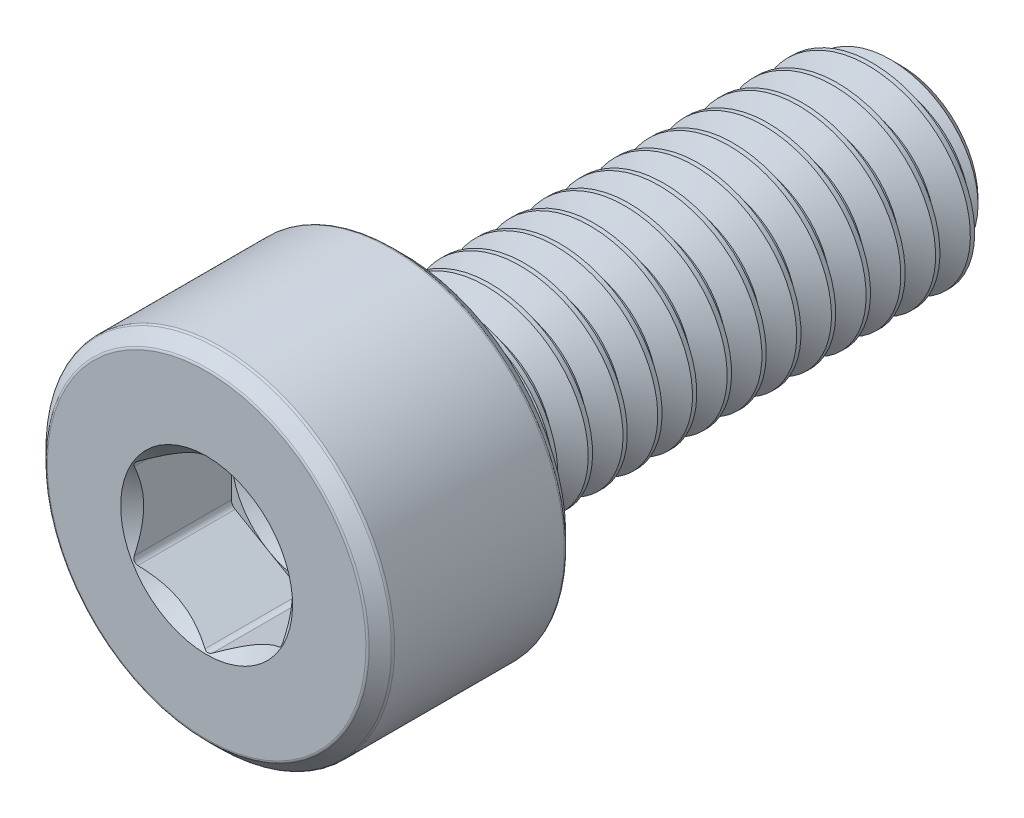
SolidWorks part; units mm, degrees
ref_plane "Front Plane" through (0, 0, 0) normal (0, 0, 1) x (1, 0, 0)
ref_plane "Top Plane" through (0, 0, 0) normal (0, 1, 0) x (1, 0, 0)
ref_plane "Right Plane" through (0, 0, 0) normal (1, 0, 0) x (0, 0, -1)
sketch "Sketch1" plane through (0, 0, 0) normal (1, 0, 0) x (0, 0, -1)
  line L0 (-7, 0) -> (7, 0) construction
  line L1 (-7, 0) -> (-7, 3.5)
  line L2 (-7, 3.5) -> (-3, 3.5)
  line L3 (-3, 3.5) -> (-3, 2)
  line L4 (-3, 2) -> (6.5453, 2)
  line L5 (6.9562, 2.0758) -> (7.3062, 1.4696) construction
  line L6 (7.3062, 1.4696) -> (7.6562, 2.0758) construction
  line L7 (7.6562, 2.0758) -> (6.9562, 2.0758) construction
  line L8 (6.5453, 2) -> (7, 1.5453)
  line L9 (7, 1.5453) -> (7, 0)
  line L10 (7, 2) -> (7.6125, 2) construction
  line L11 (7.3062, 2.0758) -> (7.3062, 2) construction
  line L12 (7.3062, 2) -> (7.3062, 1.5453) construction
  line L13 (7.3062, 1.5453) -> (7.3062, 1.4696) construction
  line L14 (7.2625, 1.5453) -> (7.35, 1.5453)
  line L15 (6.9781, 2.0379) -> (7.6344, 2.0379)
  line L16 (7.35, 1.5453) -> (7.6344, 2.0379)
  line L17 (7.2625, 1.5453) -> (6.9781, 2.0379)
  line L18 (-7, 1.5) -> (-5, 1.5)
  line L19 (-5, 1.5) -> (-5, 0)
  line L20 (4.55, 2) -> (4.55, -2) construction
  point P20 (7.3062, 2.0379)
  point P22 (4.55, -2)
  point P28 (4.55, 0)
  point P29 (6.5453, -2)
  dimension "Head Diameter" = 7
  dimension "Length" = 10
  dimension "Head Height" = 4
  dimension "Thread Size" = 4
  dimension "D1" = 45
  dimension "Thread Pitch" = 0.7
  dimension "D3" = 0.0875
  dimension "Drive Size" = 3
  dimension "D4" = 2.45
  dimension "D5" = 2
sketch "Sketch3" plane through (0, 0, 0) normal (1, 0, 0) x (0, 0, -1)
  line L0 (-7, 3.2103) -> (-7, 1.5)
  line L1 (-7, 1.5) -> (-5, 1.5)
  line L2 (-5, 1.5) -> (-5, 0)
  line L3 (-5, 0) -> (7, 0)
  line L4 (7, 0) -> (7, 1.5453)
  line L5 (7, 1.5453) -> (6.5453, 2)
  line L6 (6.5453, 2) -> (-3, 2)
  line L7 (-3, 2) -> (-3, 3.2103)
  line L8 (-3.2897, 3.5) -> (-6.7103, 3.5)
  line L9 (-6.9808, 3.2567) -> (-6.7567, 3.4808)
  line L11 (-7, 3.5) -> (-3, 3.5) construction
  line L12 (-3.2433, 3.4808) -> (-3.0192, 3.2567)
  arc A5 (-3.0192, 3.2567) -> (-3, 3.2103) centre (-3.0656, 3.2103) cw
  arc A6 (-3.2897, 3.5) -> (-3.2433, 3.4808) centre (-3.2897, 3.4344) cw
  arc A7 (-6.7103, 3.5) -> (-6.7567, 3.4808) centre (-6.7103, 3.4344) ccw
  arc A8 (-7, 3.2103) -> (-6.9808, 3.2567) centre (-6.9344, 3.2103) cw
  point P17 (-5, 3.5)
  point P29 (-7, 3.2375)
  dimension "D3" = 0.0656
  dimension "D1" = 45
  dimension "D2" = 0.2625
revolve "Revolve1" add sketch "Sketch3" angle 360 about L0
sketch "Sketch4" plane through (0, 0, 7) normal (0, 0, 1) x (1, 0, 0)
  line L1 (0, 1.7321) -> (-1.5, 0.866)
  line L2 (-1.5, 0.866) -> (-1.5, -0.866)
  line L3 (-1.5, -0.866) -> (0, -1.7321)
  line L4 (0, -1.7321) -> (1.5, -0.866)
  line L5 (1.5, -0.866) -> (1.5, 0.866)
  line L6 (1.5, 0.866) -> (0, 1.7321)
  circle A0 centre (0, 0) radius 1.5 construction
extrude "Cut-Extrude1" cut sketch "Sketch4" against normal up to vertex (2 mm away) up to point (0, 1.5, 5)
sketch "Sketch5" plane through (0, 0, 7) normal (0, 0, 1) x (1, 0, 0)
  circle A0 centre (0, 0) radius 1.7321
extrude "Cut-Extrude2" cut sketch "Sketch5" against normal up to next (2 mm away) draft 45
sketch "Sketch10" plane through (0, 0, 5) normal (0, 0, 1) x (1, 0, 0)
  line L0 (1.5, 0.866) -> (1.5, -0.866) construction
  circle A0 centre (0, 0) radius 1.5
extrude "Cut-Extrude3" cut sketch "Sketch10" against normal through all draft 60
fillet "Fillet1" radius 0.15 6 edges at (-1.5, 0.866, 6) (0, 1.7321, 6) (1.5, 0.866, 6) (1.5, -0.866, 6) (0, -1.7321, 6) (-1.5, -0.866, 6)
sketch "Sketch6" plane through (0, 0, -7) normal (0, 0, -1) x (-1, 0, 0)
  circle A0 centre (0, 0) radius 2 construction
  circle A1 centre (0, 0) radius 2
curve "Helix/Spiral1" pitch 0.7 height 10.7 radius 2 centre (0, 0, -7) axis (0, 0, 1) start towards (0, 1, 0)
sketch "Sketch7" plane through (0, 0, 0) normal (1, 0, 0) x (0, 0, -1)
  line L0 (7.2625, 1.5453) -> (7.35, 1.5453) construction
  line L1 (7.2625, 1.5453) -> (6.9781, 2.0379) construction
  line L2 (6.9781, 2.0379) -> (7.6344, 2.0379) construction
  line L3 (7.35, 1.5453) -> (7.6344, 2.0379) construction
  line L4 (7.2625, 1.5453) -> (7.35, 1.5453)
  line L5 (7.2625, 1.5453) -> (6.9781, 2.0379)
  line L6 (6.9781, 2.0379) -> (7.6344, 2.0379)
  line L7 (7.35, 1.5453) -> (7.6344, 2.0379)
sweep "Cut-Sweep1" cut profiles "Sketch7" path "Helix/Spiral1" align with end faces yes
sketch "Sketch11" plane through (0, 0, 0) normal (1, 0, 0) x (0, 0, -1)
  line L0 (-3, 2.175) -> (-2.825, 2) construction
  line L1 (-3, 3.5) -> (-3, 2) construction
  line L2 (-3, 2) -> (6.5453, 2) construction
  line L3 (-2.825, 2) -> (-2.65, 2)
  line L4 (-2.65, 2) -> (-0.65, 0)
  line L5 (-7, 0) -> (7, 0) construction
  line L6 (-0.65, 0) -> (-3, 0)
  line L7 (-3, 0) -> (-3, 2.175) construction
  line L8 (-3, 2.175) -> (-4.134, 2.175)
  line L9 (-4.134, 2.175) -> (-4.134, 0)
  line L10 (-4.134, 0) -> (-3, 0)
  arc A0 (-2.825, 2) -> (-3, 2.175) centre (-2.825, 2.175) cw
  dimension "D1" = 45
  dimension "D2" = 0.175
  dimension "D3" = 45
  dimension "D4" = 0.35
revolve "Revolve2" add sketch "Sketch11" angle 360 about L6
equation "\"D3@Sketch1\" = \"Thread Pitch@Sketch1\" / 8"
equation "\"D4@Sketch1\" = \"Thread Pitch@Sketch1\" * 3.5"
equation "\"D3@Helix/Spiral1\" = \"Length@Sketch1\" + \"Thread Pitch@Sketch1\""
equation "\"D4@Helix/Spiral1\" = \"Thread Pitch@Sketch1\""
equation "\"D5@Sketch1\"=\"Head Height@Sketch1\"*0.5"
equation "\"D2@Sketch3\"=\"Head Diameter@Sketch1\" *0.0375"
equation "\"D2@Sketch11\"=\"Thread Pitch@Sketch1\" / 4"
equation "\"D4@Sketch11\"=\"Thread Pitch@Sketch1\"/2"
equation "\"D1@Fillet1\"=\"Drive Size@Sketch1\"*0.05"
equation "\"D1@Fillet1\" = \"Drive Size@Sketch1\" * 0.05"
equation "\"D3@Sketch3\"=\"D2@Sketch3\"*0.25"
